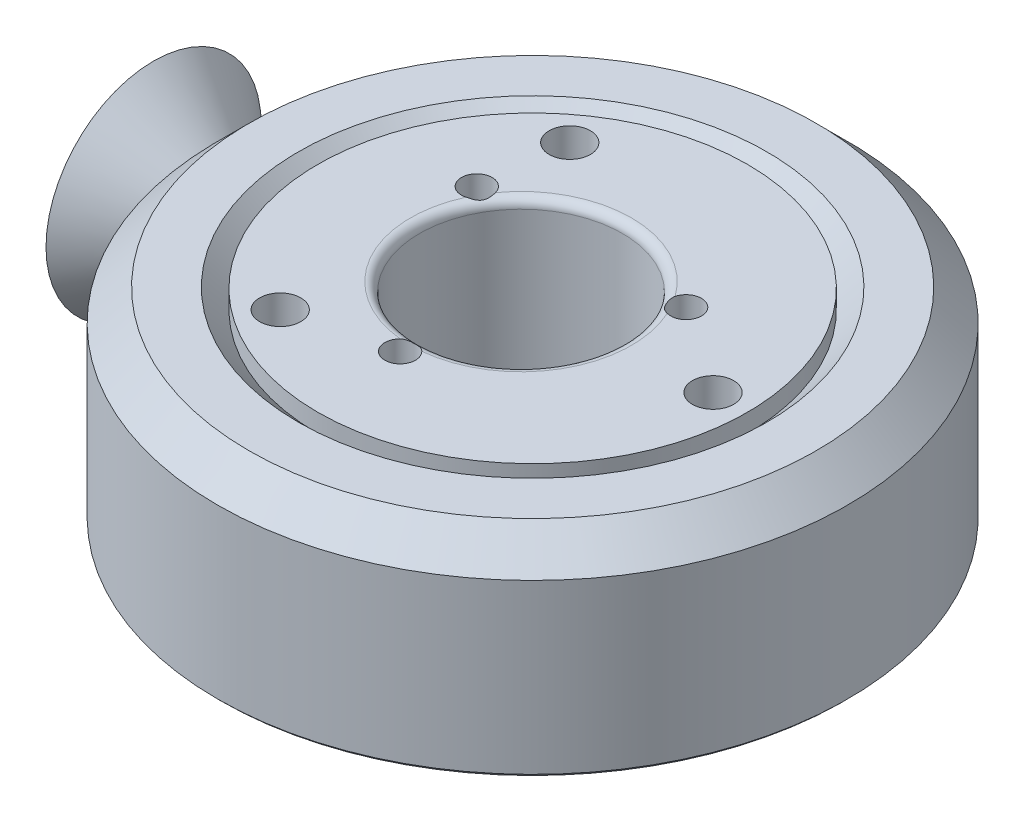
SolidWorks part; units mm, degrees
material "AISI 1020 Steel, Cold Rolled"
ref_plane "Front Plane" through (0, 0, 0) normal (0, 0, 1) x (1, 0, 0)
ref_plane "Top Plane" through (0, 0, 0) normal (0, 1, 0) x (1, 0, 0)
ref_plane "Right Plane" through (0, 0, 0) normal (1, 0, 0) x (0, 0, -1)
other "Center of Mass"
sketch "Sketch1" plane through (0, 0, 0) normal (0, 1, 0) x (1, 0, 0)
  circle A0 centre (0, 0) radius 34.925
  circle A1 centre (0, 0) radius 23.8125
  dimension "D1" = 69.85
  dimension "D2" = 47.625
extrude "Boss-Extrude1" add sketch "Sketch1" along normal mid plane 22.479
chamfer "Chamfer1" distance 2.159 angle 45 2 edges at (0, -11.2395, 23.8125) (0, 11.2395, 23.8125)
chamfer "Chamfer2" distance 3.4798 angle 45 1 edges at (0, 11.2395, 34.925)
chamfer "Chamfer3" distance 0.381 angle 45 1 edges at (0, -11.2395, 34.925)
sketch "Sketch2" plane through (0, 0, 0) normal (0, 1, 0) x (1, 0, 0)
  line L0 (-42.037, 11.9126) -> (-42.037, 0)
  line L1 (-42.037, 0) -> (-17.1196, 0)
  line L2 (-17.1196, 0) -> (-17.1196, 5.3693)
  line L3 (-17.1196, 5.3693) -> (-34.5098, 5.3693)
  line L4 (-34.5098, 5.3693) -> (-42.037, 11.9126)
  circle A0 centre (0, 0) radius 34.925 construction
  point P7 (34.925, 0)
  dimension "D1" = 24.9174
  dimension "D2" = 76.962
  dimension "D3" = 41
  dimension "D4" = 11.9126
revolve "Revolve1" add sketch "Sketch2" angle 360 about L1
other "Center of Mass Reference Point1"
chamfer "Chamfer4" distance 1.27 angle 45 1 edges at (-17.1196, 0, 5.3693)
sketch "Sketch3" plane through (0, 0, 0) normal (0, 1, 0) x (1, 0, 0)
  circle A0 centre (0, 0) radius 23.8125
  point P1 (-23.6959, 2.3537)
  point P4 (-23.8109, 0)
  dimension "D1" = 47.625
extrude "Boss-Extrude2" add sketch "Sketch3" along normal mid plane 22.225 separate body
sketch "Sketch4" plane through (0, 11.1125, 0) normal (0, 1, 0) x (1, 0, 0)
  circle A0 centre (-1.2893, 0) radius 11.25
  dimension "D1" = 22.5
  dimension "D2" = 1.2893
extrude "Cut-Extrude1" cut sketch "Sketch4" against normal through all both and the other way through all
ref_axis "Axis1" through (-1.2893, -11.1125, 0) along (0, 1, 0)
sketch "Sketch6" plane through (-42.037, 0, 0) normal (-1, 0, 0) x (0, 0, 1)
  line L1 (-4.6194, 0) -> (-2.3097, -4.0005)
  line L2 (-2.3097, -4.0005) -> (2.3097, -4.0005)
  line L3 (2.3097, -4.0005) -> (4.6194, 0)
  line L4 (4.6194, 0) -> (2.3097, 4.0005)
  line L5 (2.3097, 4.0005) -> (-2.3097, 4.0005)
  line L6 (-2.3097, 4.0005) -> (-4.6194, 0)
  circle A0 centre (0, 0) radius 4.0005 construction
  dimension "D1" = 8.001
extrude "Cut-Extrude3" cut sketch "Sketch6" against normal blind 6.35
sketch "Sketch9" plane through (0, 0, 0) normal (0, 0, 1) x (1, 0, 0)
  line L0 (-23.8125, 6.604) -> (-15.8125, 6.604)
  line L1 (-15.8125, 6.604) -> (-15.8125, 0)
  line L2 (-15.8125, 0) -> (-23.8125, 0)
  line L3 (-23.8125, 0) -> (-23.8125, 6.604)
  line L4 (-23.8125, 11.1125) -> (-23.8125, -11.1125) construction
  point P2 (-23.8125, 1.226)
  dimension "D1" = 6.604
  dimension "D2" = 8
revolve "Cut-Revolve1" cut sketch "Sketch9" angle 360 about L2
sketch "Sketch12" plane through (0, -11.1125, 0) normal (0, -1, 0) x (1, 0, 0)
  circle A0 centre (-1.2893, 0) radius 11.25 construction
  circle A1 centre (-1.2893, 0) radius 11.25
  circle A2 centre (0, 0) radius 27.8125
  circle A5 centre (0, 0) radius 23.8125 construction
  point P5 (0, 0)
  dimension "D1" = 4
extrude "Boss-Extrude5" add sketch "Sketch12" along normal blind 2
sketch "Sketch13" plane through (0, -13.1125, 0) normal (0, -1, 0) x (1, 0, 0)
  circle A0 centre (-1.2893, 0) radius 11.25 construction
  circle A1 centre (-1.2893, 0) radius 11.25
  circle A2 centre (-1.2893, 0) radius 15.25
  dimension "D1" = 4
extrude "Boss-Extrude6" add sketch "Sketch13" along normal blind 7
sketch "Sketch14" plane through (0, -20.1125, 0) normal (0, -1, 0) x (1, 0, 0)
  circle A0 centre (-1.2893, 0) radius 11.25 construction
  circle A1 centre (-1.2893, 0) radius 11.25
  circle A2 centre (-1.2893, 0) radius 17.25
  circle A3 centre (-1.2893, 0) radius 15.25 construction
  dimension "D1" = 2
extrude "Boss-Extrude7" add sketch "Sketch14" along normal blind 2
sketch "Sketch15" plane through (0, -13.1125, 0) normal (0, -1, 0) x (1, 0, 0)
  line L0 (-11.9339, 16.0493) -> (0, 0) construction
  line L1 (0, 0) -> (-11.9339, -16.0493) construction
  line L2 (0, 0) -> (20, 0) construction
  line L3 (-11.9339, 16.0493) -> (-1.2893, 16.0493) construction
  line L4 (-1.2893, 16.0493) -> (9.3554, 16.0493) construction
  line L5 (9.3554, 16.0493) -> (20, 16.0493) construction
  line L6 (20, 16.0493) -> (20, 0) construction
  circle A0 centre (-11.9339, 16.0493) radius 2.286
  circle A1 centre (20, 0) radius 2.286
  circle A2 centre (-11.9339, -16.0493) radius 2.286
  point P6 (0, 0)
  point P11 (0, 0)
  point P14 (-12.1275, 16.3878)
  dimension "D1" = 4.572
  dimension "D2" = 20
extrude "Cut-Extrude5" cut sketch "Sketch15" against normal through all
sketch "Sketch16" plane through (0, -22.1125, 0) normal (0, -1, 0) x (1, 0, 0)
  line L0 (10.3154, -6.7) -> (-1.2893, 0) construction
  line L1 (-1.2893, 0) -> (-12.894, -6.7) construction
  line L2 (-1.2893, 0) -> (-1.2893, 13.4) construction
  circle A0 centre (-12.894, -6.7) radius 1.7
  circle A1 centre (-1.2893, 13.4) radius 1.7
  circle A2 centre (10.3154, -6.7) radius 1.7
  circle A3 centre (-1.2893, 0) radius 11.25 construction
  point P6 (-3.1173, -0.5767)
  point P11 (-13.6942, -5.0675)
  dimension "D1" = 120
  dimension "D3" = 3.4
  dimension "D2" = 120
  dimension "D4" = 13.4
extrude "Cut-Extrude6" cut sketch "Sketch16" against normal through all
sketch "Sketch17" plane through (0, 0, 0) normal (0, 0, 1) x (1, 0, 0)
  line L1 (-12.5393, -16.1125) -> (-12.5393, -8.2605)
  line L2 (-12.5393, -16.1125) -> (-11.1251, -14.6983)
  line L3 (-11.1251, -14.6983) -> (-11.1251, -9.6747)
  line L4 (-11.1251, -9.6747) -> (-12.5393, -8.2605)
  line L6 (-12.5393, -22.1125) -> (9.9607, -22.1125) construction
  line L7 (-12.5393, 11.1125) -> (-12.5393, -22.1125) construction
  line L8 (31.4452, 11.2395) -> (-31.4452, 11.2395) construction
  point P4 (-9.7798, -11.2395)
  point P7 (-11.194, -1.9001)
  point P8 (0, 0)
  point P11 (-11.194, -9.8253)
  point P12 (-11.194, -9.8253)
  dimension "D1" = 2
  dimension "D2" = 45
  dimension "D3" = 6
  dimension "D4" = 19.5
revolve "Revolve2" add sketch "Sketch17" angle 360 about axis through (-1.2893, -11.1125, 0) along (0, 1, 0)
chamfer "Chamfer5" distance 2 angle 45 6 edges at (-12.894, -22.1125, -8.4) (-11.9339, -13.1125, 13.7633) (20, -13.1125, -2.286) (-11.9339, -13.1125, -18.3353) (10.3154, -22.1125, -8.4) (-1.2893, -22.1125, 11.7)
fillet "Fillet1" radius 1 4 edges at (-1.2893, 11.1125, 11.25) (-1.2893, -22.1125, -11.25) (8.4535, -22.1125, 5.625) (-11.0321, -22.1125, 5.625)
ref_plane "Plane1" through (0, -13.1125, 0) normal (0, -1, 0) x (-1, 0, 0)
split "Split1" trim tools "Plane1" bodies to split 130 resulting bodies 131 132
